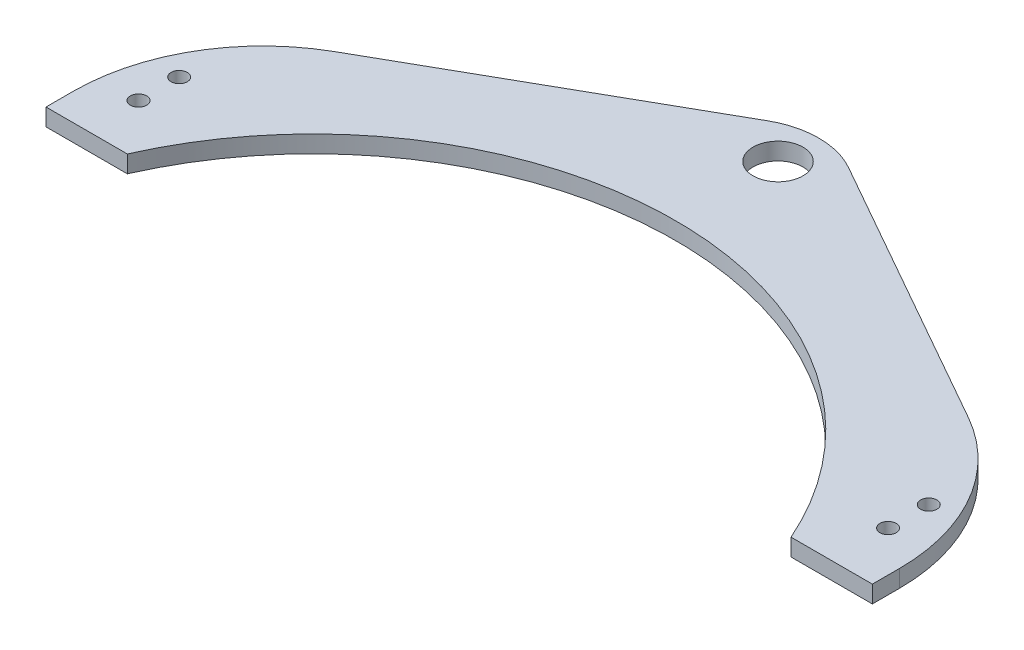
SolidWorks part; units mm, degrees
ref_plane "Front Plane" through (0, 0, 0) normal (0, 0, 1) x (1, 0, 0)
ref_plane "Top Plane" through (0, 0, 0) normal (0, 1, 0) x (1, 0, 0)
ref_plane "Right Plane" through (0, 0, 0) normal (1, 0, 0) x (0, 0, -1)
sketch "Sketch1" plane through (0, 0, 0) normal (0, 1, 0) x (1, 0, 0)
  line L0 (0, 0) -> (122.4, 0)
  line L1 (61.2, 0) -> (61.2, 39.9)
  line L2 (122.4, 0) -> (137.4, 0)
  line L3 (0, 0) -> (-15, 0)
  line L4 (137.4, 0) -> (137.4, 16.6577)
  line L5 (-15, 0) -> (-15, 16.6577)
  line L6 (61.2, 0) -> (61.2, 58.8)
  line L7 (61.2, 58.8) -> (61.2, 66.3)
  line L8 (61.2, 66.3) -> (61.2465, 66.3)
  line L9 (61.2, 66.3) -> (61.1535, 66.3)
  line L10 (68.6399, 64.3514) -> (129.7934, 29.709)
  line L11 (53.7601, 64.3514) -> (-7.3934, 29.709)
  line L12 (129.9, 0) -> (129.9, 10.4)
  line L13 (129.9, 10.4) -> (129.9, 17.9)
  line L15 (119.6512, 35.4544) -> (68.6399, 64.3514)
  line L16 (137.4, 5.0012) -> (137.4, 0)
  line L17 (53.7601, 64.3514) -> (2.7488, 35.4544)
  line L18 (-15, 5.0012) -> (-15, 0)
  line L19 (-7.5, 17.0643) -> (-7.5, 9.5643)
  arc A0 (0, 0) -> (122.4, 0) centre (61.2, -26.9726) cw
  circle A1 centre (61.2, 58.8) radius 4.6
  arc A2 (61.2465, 66.3) -> (68.6399, 64.3514) centre (61.2465, 51.3) cw
  arc A3 (61.1535, 66.3) -> (53.7601, 64.3514) centre (61.1535, 51.3) ccw
  arc A4 (-15, 16.6577) -> (-7.3934, 29.709) centre (0, 16.6577) cw
  arc A5 (137.4, 16.6577) -> (129.7934, 29.709) centre (122.4, 16.6577) ccw
  circle A6 centre (129.9, 17.9) radius 1.5
  circle A7 centre (129.9, 10.4) radius 1.5
  circle A8 centre (-7.5, 17.0643) radius 1.5
  arc A10 (119.6512, 35.4544) -> (137.4, 5.0012) centre (102.4, 5.0012) cw
  arc A11 (2.7488, 35.4544) -> (-15, 5.0012) centre (20, 5.0012) ccw
  circle A12 centre (-7.5, 9.5643) radius 1.5
  point P17 (65.2, 66.3)
  point P20 (57.2, 66.3)
  point P23 (-15, 25.4)
  point P26 (137.4, 25.4)
  point P41 (137.4, 25.4)
  point P44 (-15, 25.4)
  dimension "D8" = 7.5
  dimension "D11" = 15
  dimension "D12" = 15
  dimension "D15" = 7.5
  dimension "D16" = 35
  dimension "D1" = 122.4
  dimension "D2" = 39.9
  dimension "D3" = 15
  dimension "D4" = 15
  dimension "D5" = 25.4
  dimension "D6" = 25.4
  dimension "D7" = 58.8
  dimension "D9" = 4
  dimension "D10" = 4
  dimension "D13" = 10.4
  dimension "D14" = 7.5
extrude "Boss-Extrude2" add sketch "Sketch1" along normal blind 3.175 contours L11 A11 L5 L3 A8 A0 L6 A1 L7 L9 A3 | A10 L10 A2 L8 L7 A1 L6 A0 L2 A7 A6 L4 region at (21.8428, 0, -33.5058) region at (100.5572, 0, -33.4988)
